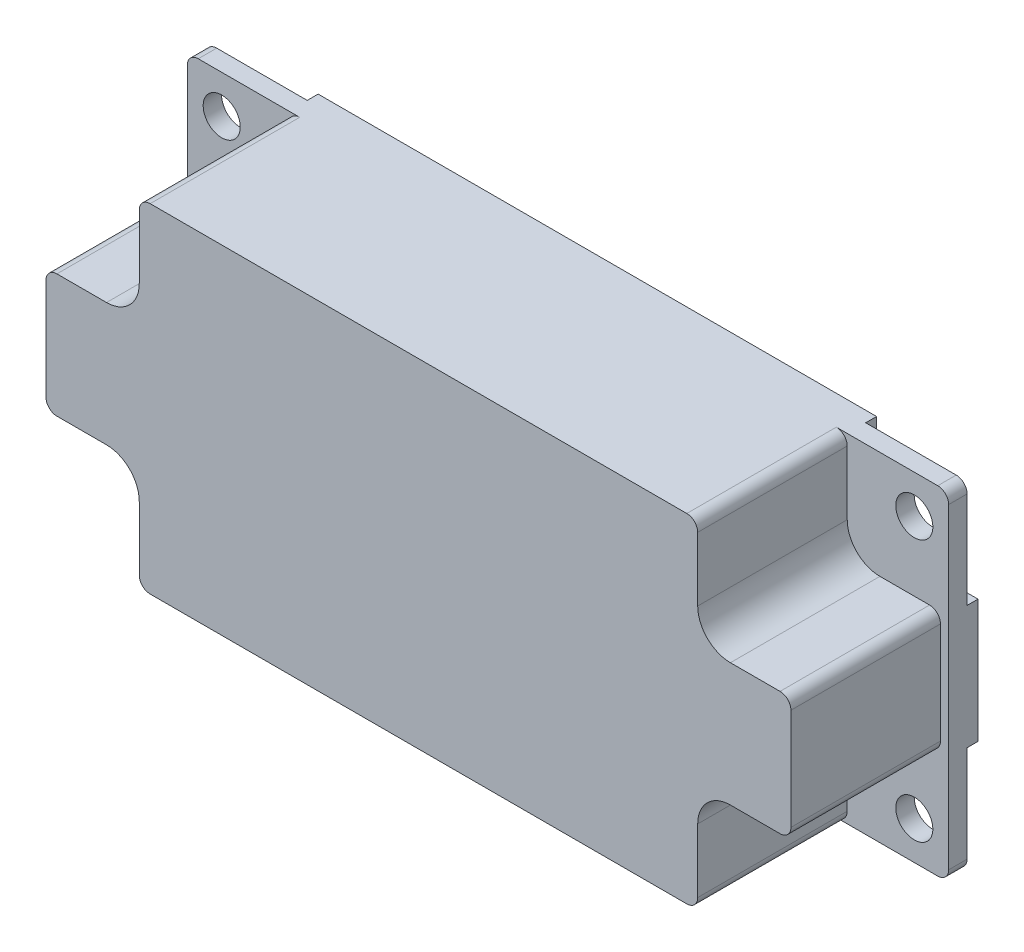
SolidWorks part; units mm, degrees
ref_plane "前视基准面" through (0, 0, 0) normal (0, 0, 1) x (1, 0, 0)
ref_plane "上视基准面" through (0, 0, 0) normal (0, 1, 0) x (1, 0, 0)
ref_plane "右视基准面" through (0, 0, 0) normal (1, 0, 0) x (0, 0, -1)
sketch "草图1" plane through (0, 0, 0) normal (0, 0, 1) x (1, 0, 0)
  line L1 (34.9, -15.5) -> (-34.9, -15.5)
  line L2 (34.9, -15.5) -> (34.9, 15.5)
  line L3 (34.9, 15.5) -> (-34.9, 15.5)
  line L4 (-34.9, -15.5) -> (-34.9, 15.5)
  line L5 (34.9, -15.5) -> (-34.9, 15.5) construction
  line L6 (34.9, 15.5) -> (-34.9, -15.5) construction
  point P0 (0, 0)
  dimension "D1" = 69.8
  dimension "D2" = 31
extrude "凸台-拉伸1" add sketch "草图1" along normal blind 16.4
sketch "草图2" plane through (0, 0, 0) normal (0, 0, -1) x (-1, 0, 0)
  line L0 (0, 0) -> (-34.9, 0) construction
  line L1 (-34.9, 15.5) -> (-25.6, 15.5)
  line L2 (-34.9, 15.5) -> (-34.9, 5.65)
  line L3 (-34.9, 5.65) -> (-25.6, 5.65)
  line L4 (-25.6, 15.5) -> (-25.6, 5.65)
  line L5 (-34.9, -15.5) -> (-34.9, 15.5) construction
  line L6 (-25.6, -15.5) -> (-25.6, -5.65)
  line L7 (-34.9, -5.65) -> (-25.6, -5.65)
  line L8 (-34.9, -15.5) -> (-34.9, -5.65)
  line L9 (-34.9, -15.5) -> (-25.6, -15.5)
  line L10 (0, 0) -> (0, 19.4757) construction
  line L11 (34.9, -15.5) -> (25.6, -15.5)
  line L12 (34.9, -15.5) -> (34.9, -5.65)
  line L13 (34.9, -5.65) -> (25.6, -5.65)
  line L14 (25.6, -15.5) -> (25.6, -5.65)
  line L15 (25.6, 15.5) -> (25.6, 5.65)
  line L16 (34.9, 5.65) -> (25.6, 5.65)
  line L17 (34.9, 15.5) -> (34.9, 5.65)
  line L18 (34.9, 15.5) -> (25.6, 15.5)
  dimension "D1" = 11.3
  dimension "D2" = 9.3
extrude "切除-拉伸1" cut sketch "草图2" against normal blind 1
sketch "草图3" plane through (0, 0, 16.4) normal (0, 0, 1) x (1, 0, 0)
  line L0 (34.9, -15.5) -> (34.9, 15.5) construction
  line L1 (-34.9, -15.5) -> (34.9, -15.5) construction
  line L2 (34.9, 15.5) -> (-34.9, 15.5) construction
  line L3 (-34.9, 15.5) -> (-34.9, -15.5) construction
  line L4 (-34.9, -5.65) -> (-25.6, -5.65) construction
  line L5 (-25.6, -5.65) -> (-25.6, -15.5) construction
  line L6 (25.6, -15.5) -> (25.6, -5.65) construction
  line L7 (25.6, -5.65) -> (34.9, -5.65) construction
  line L8 (34.9, 5.65) -> (25.6, 5.65) construction
  line L9 (25.6, 5.65) -> (25.6, 15.5) construction
  line L10 (-25.6, 15.5) -> (-25.6, 5.65) construction
  line L11 (-25.6, 5.65) -> (-34.9, 5.65) construction
  line L12 (34.9, -15.5) -> (34.9, -5.65)
  line L13 (-34.9, -15.5) -> (-25.6, -15.5)
  line L14 (34.9, 15.5) -> (25.6, 15.5)
  line L15 (-34.9, 15.5) -> (-34.9, 5.65)
  line L16 (-34.9, -5.65) -> (-25.6, -5.65)
  line L17 (-25.6, -5.65) -> (-25.6, -15.5)
  line L18 (25.6, -15.5) -> (25.6, -5.65)
  line L19 (25.6, -5.65) -> (34.9, -5.65)
  line L20 (34.9, 5.65) -> (25.6, 5.65)
  line L21 (25.6, 5.65) -> (25.6, 15.5)
  line L22 (-25.6, 15.5) -> (-25.6, 5.65)
  line L23 (-25.6, 5.65) -> (-34.9, 5.65)
  line L24 (-25.6, 15.5) -> (-34.9, 15.5)
  line L25 (-34.9, -5.65) -> (-34.9, -15.5)
  line L26 (25.6, -15.5) -> (34.9, -15.5)
  line L27 (34.9, 5.65) -> (34.9, 15.5)
extrude "切除-拉伸2" cut sketch "草图3" against normal offset from surface (13.71 mm away) 1.69 up to face at (30.25, 10.575, 1)
sketch "草图4" plane through (0, 0, 0) normal (0, 0, -1) x (-1, 0, 0)
  line L0 (-2.1, 0) -> (9, 0) construction
  line L1 (-2.1, 13.6) -> (9, 13.6)
  line L2 (-2.1, -13.6) -> (9, -13.6)
  line L3 (34.9, 5.65) -> (34.9, -5.65) construction
  arc A0 (-2.1, 13.6) -> (-2.1, -13.6) centre (-2.1, 0) ccw
  arc A1 (9, -13.6) -> (9, 13.6) centre (9, 0) ccw
  point P3 (3.45, 0)
  point P9 (22.6, 0)
  point P10 (-15.7, 0)
  point P13 (34.9, 0)
  dimension "D3" = 12.3
  dimension "D1" = 27.2
  dimension "D2" = 38.3
extrude "切除-拉伸3" cut sketch "草图4" against normal blind 2
hole_wizard "M3 间隙孔1" positions "草图6" profile "草图7" hole size "M3" standard "GB" end condition up to next
sketch "草图6" plane through (0, 0, 1) normal (0, 0, -1) x (-1, 0, 0)
  line L0 (0, 0) -> (0, 10.4597) construction
  line L2 (0, 0) -> (8.2957, 0) construction
  point P0 (31.75, 12)
  point P2 (31.75, -12)
  point P4 (-31.75, -12)
  point P6 (-31.75, 12)
  dimension "D1" = 24
  dimension "D2" = 63.5
sketch "草图7" plane through (-31.75, 12, 1) normal (1, 0, 0) x (0, 1, 0)
  line L0 (0, 0) -> (0, 1.69)
  line L1 (0, 1.69) -> (1.7, 1.69)
  line L2 (1.7, 1.69) -> (1.7, 0)
  line L5 (1.7, 0) -> (0, 0)
  line L11 (0, -6.35) -> (0, 107.95) construction
  dimension "通孔孔直径" = 3.4
  dimension "通孔孔深度" = 1.69
sketch "草图8" plane through (0, 0, 16.4) normal (0, 0, 1) x (1, 0, 0)
  line L0 (-25.6, -5.65) -> (-34.9, -5.65) construction
  line L1 (-34.9, 5.65) -> (-34.15, 5.65)
  line L2 (-34.9, 5.65) -> (-34.9, -5.65)
  line L3 (-34.9, -5.65) -> (-34.15, -5.65)
  line L4 (-34.15, 5.65) -> (-34.15, -5.65)
  line L5 (34.9, -5.65) -> (25.6, -5.65) construction
  line L6 (34.9, 5.65) -> (34.15, 5.65)
  line L7 (34.9, 5.65) -> (34.9, -5.65)
  line L8 (34.9, -5.65) -> (34.15, -5.65)
  line L9 (34.15, 5.65) -> (34.15, -5.65)
  line L10 (0, 0) -> (0, 9.6652) construction
  dimension "D1" = 68.3
extrude "切除-拉伸5" cut sketch "草图8" against normal up to surface (13.71 mm away) up to face at (-33.45, -12, 2.69)
sketch "草图9" plane through (-34.15, 0, 0) normal (-1, 0, 0) x (0, 0, 1)
  circle A0 centre (6.2323, 0) radius 0.4373
  circle A1 centre (7.5004, 0) radius 0.4373
extrude "凸台-拉伸3" add sketch "草图9" along normal blind 2
fillet "圆角1" radius 3 12 edges at (-3.45, -13.6, 2) (15.7, 0, 2) (-3.45, 13.6, 2) (-22.6, 0, 2) (-25.6, -5.65, 0.5) (-25.6, 5.65, 0.5) (25.6, -5.65, 0.5) (25.6, 5.65, 0.5) (-25.6, 5.65, 9.545) (25.6, 5.65, 9.545) (25.6, -5.65, 9.545) (-25.6, -5.65, 9.545)
fillet "圆角2" radius 1 12 edges at (-34.9, 15.5, 1.845) (-34.9, -15.5, 1.845) (-25.6, -15.5, 9.545) (-34.15, -5.65, 9.545) (-34.15, 5.65, 9.545) (-25.6, 15.5, 9.545) (25.6, -15.5, 9.545) (25.6, 15.5, 9.545) (34.15, 5.65, 9.545) (34.15, -5.65, 9.545) (34.9, -15.5, 1.845) (34.9, 15.5, 1.845)
